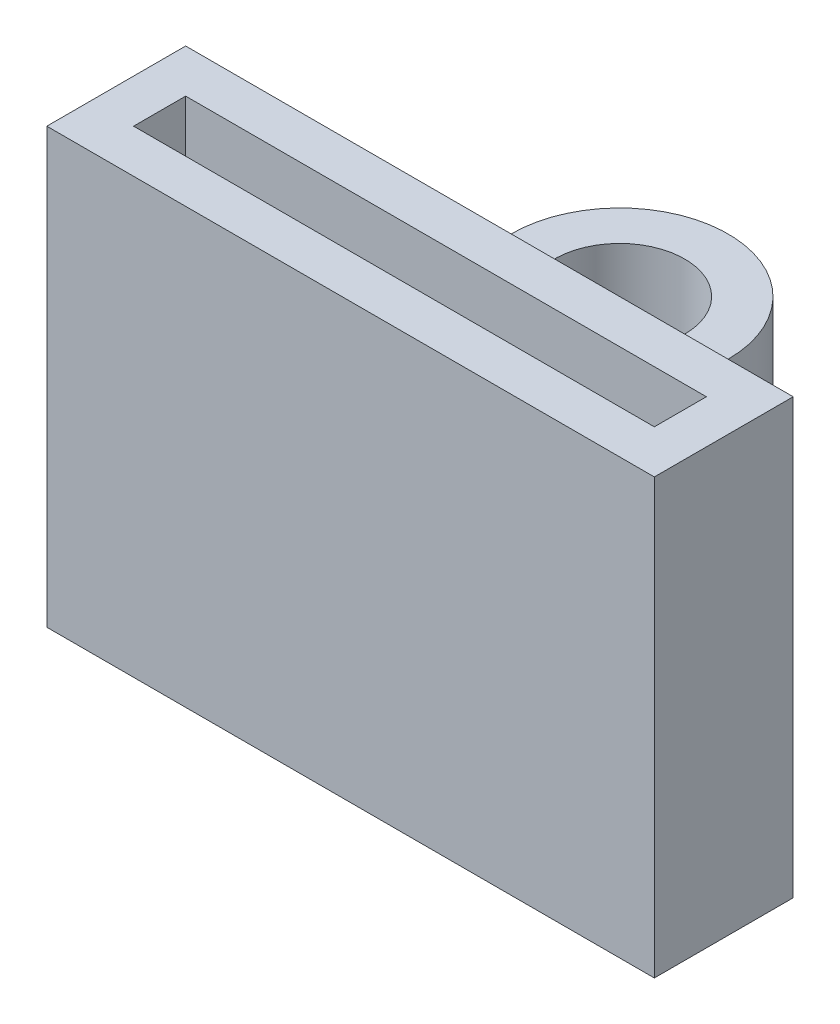
SolidWorks part; units mm, degrees
ref_plane "Front Plane" through (0, 0, 0) normal (0, 0, 1) x (1, 0, 0)
ref_plane "Top Plane" through (0, 0, 0) normal (0, 1, 0) x (1, 0, 0)
ref_plane "Right Plane" through (0, 0, 0) normal (1, 0, 0) x (0, 0, -1)
sketch "Sketch1" plane through (0, 0, 0) normal (0, 1, 0) x (1, 0, 0)
  line L0 (-2.5, 4.6) -> (-2.5, 1.6)
  line L5 (-6, 0.6) -> (6, 0.6)
  line L6 (-6, 0.6) -> (-6, -0.6)
  line L7 (-6, -0.6) -> (6, -0.6)
  line L8 (6, 0.6) -> (6, -0.6)
  line L9 (-6, 0.6) -> (6, -0.6) construction
  line L10 (-6, -0.6) -> (6, 0.6) construction
  line L11 (-7, 1.6) -> (7, 1.6)
  line L12 (-7, 1.6) -> (-7, -1.6)
  line L13 (-7, -1.6) -> (7, -1.6)
  line L14 (7, 1.6) -> (7, -1.6)
  line L15 (-7, 1.6) -> (7, -1.6) construction
  line L16 (-7, -1.6) -> (7, 1.6) construction
  line L17 (2.5, 4.6) -> (2.5, 1.6)
  circle A0 centre (0, 4.6) radius 1.5
  arc A1 (2.5, 4.6) -> (-2.5, 4.6) centre (0, 4.6) ccw
  point P0 (0, 0)
  point P7 (0, 0)
  dimension "D5" = 3
  dimension "D6" = 3
  dimension "D7" = 5
  dimension "D1" = 3.2
  dimension "D2" = 14
  dimension "D3" = 12
  dimension "D4" = 1.2
extrude "Boss-Extrude1" add sketch "Sketch1" along normal mid plane 10 contours L14 L11 L12 L13 L5 L8 L7 L6 region at (0, 0, -1.4564)
extrude "Boss-Extrude2" add sketch "Sketch1<3>" along normal blind 2 and the other way blind 5 contours L17 A1 L0 L11 A0 region at (0, 0, -7.0257)
sketch "Sketch1<3>" plane through (0, 0, 0) normal (0, 1, 0) x (1, 0, 0) same geometry as "Sketch1"
